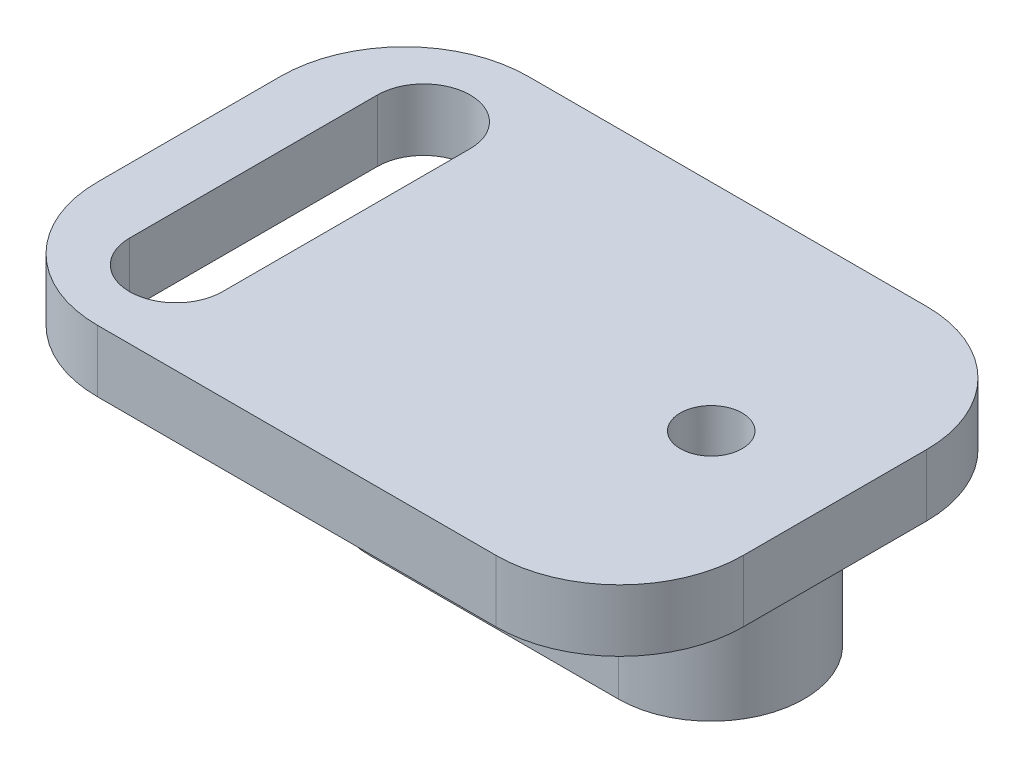
SolidWorks part; units mm, degrees
ref_plane "Front Plane" through (0, 0, 0) normal (0, 0, 1) x (1, 0, 0)
ref_plane "Top Plane" through (0, 0, 0) normal (0, 1, 0) x (1, 0, 0)
ref_plane "Right Plane" through (0, 0, 0) normal (1, 0, 0) x (0, 0, -1)
sketch "Sketch1" plane through (0, 0, 0) normal (0, 1, 0) x (1, 0, 0)
  line L0 (-10, 0) -> (10, 0) construction
  line L1 (-22.1615, -17.3911) -> (10, -17.3911)
  line L2 (-32.1615, -7.3911) -> (-32.1615, 7.3911)
  line L3 (-22.1615, 17.3911) -> (10, 17.3911)
  line L4 (20, -7.3911) -> (20, 7.3911)
  line L5 (-17.5, 0) -> (-32.1615, 0) construction
  line L7 (-10, 7.5) -> (10, 7.5)
  line L8 (-10, -7.5) -> (10, -7.5)
  line L9 (-23.2016, 10) -> (-23.2016, -10) construction
  line L10 (-19.4516, 10) -> (-19.4516, -10)
  line L11 (-26.9516, 10) -> (-26.9516, -10)
  arc A0 (-10, 7.5) -> (-10, -7.5) centre (-10, 0) ccw
  arc A1 (10, -7.5) -> (10, 7.5) centre (10, 0) ccw
  arc A2 (-22.1615, -17.3911) -> (-32.1615, -7.3911) centre (-22.1615, -7.3911) cw
  arc A3 (-32.1615, 7.3911) -> (-22.1615, 17.3911) centre (-22.1615, 7.3911) cw
  arc A4 (10, -17.3911) -> (20, -7.3911) centre (10, -7.3911) ccw
  arc A5 (10, 17.3911) -> (20, 7.3911) centre (10, 7.3911) cw
  arc A6 (-19.4516, 10) -> (-26.9516, 10) centre (-23.2016, 10) ccw
  arc A7 (-26.9516, -10) -> (-19.4516, -10) centre (-23.2016, -10) ccw
  point P0 (0, 0)
  point P3 (0, 0)
  point P8 (0, 0)
  point P27 (-23.2016, 0)
  dimension "D1" = 10
  dimension "D2" = 10
  dimension "D5" = 7.5
extrude "Boss-Extrude1" add sketch "Sketch1" along normal blind 5 contours A5 L3 A3 L2 A2 L1 A4 L4 A7 L11 A6 L10 A1 L8 A0 L7 | L8 A1 L7 A0 region at (-28.7893, 0, 14.0188) region at (0, 0, 0)
extrude "Boss-Extrude2" add sketch "Sketch1<3>" against normal blind 10 contours L8 A1 L7 A0 region at (0, 0, 0)
sketch "Sketch1<3>" plane through (0, 0, 0) normal (0, 1, 0) x (1, 0, 0) same geometry as "Sketch1"
sketch "Sketch3" plane through (0, -10, 0) normal (0, -1, 0) x (1, 0, 0)
  line L0 (10, -7.5) -> (10, 7.5) construction
  arc A0 (10, -7.5) -> (10, 7.5) centre (10, 0) ccw construction
  arc A1 (10, -7.5) -> (10, 7.5) centre (10, 0) ccw construction
  circle A2 centre (10, 0) radius 2.5
extrude "Cut-Extrude1" cut sketch "Sketch3" against normal blind 16
